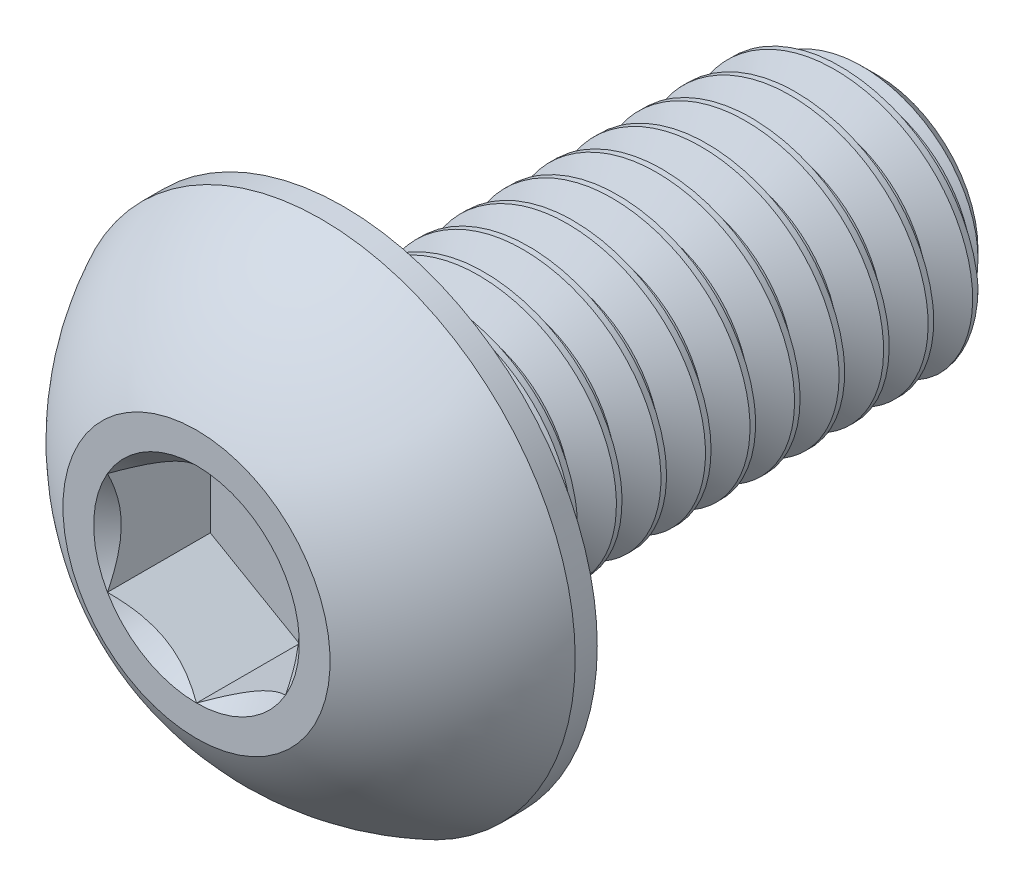
SolidWorks part; units mm, degrees
ref_plane "Front" through (0, 0, 0) normal (0, 0, 1) x (1, 0, 0)
ref_plane "Top" through (0, 0, 0) normal (0, 1, 0) x (1, 0, 0)
ref_plane "Right" through (0, 0, 0) normal (1, 0, 0) x (0, 0, -1)
sketch "Sketch1" plane through (0, 0, 0) normal (1, 0, 0) x (0, 0, -1)
  line L2 (1.65, 1.5) -> (7.65, 1.5)
  line L3 (7.65, 1.5) -> (7.65, 0)
  line L4 (7.65, 0) -> (1.65, 0)
  line L6 (1.4025, 2.85) -> (1.65, 2.85) construction
  line L7 (7.65, 1.5) -> (7.65, -1.5) construction
  line L8 (0, 0) -> (1.65, 0) construction
  line L9 (1.65, 2.85) -> (1.65, -2.85) construction
  line L11 (1.65, 1.5) -> (1.65, 0)
  line L13 (0, 1) -> (0, -1) construction
  line L14 (0, 1) -> (0, 1.5) construction
  line L15 (7.65, -1.5) -> (7.15, -1.5) construction
  arc A3 (0, 1.5) -> (1.4025, 2.85) centre (2.7948, 0) cw construction
  dimension "D1" = 0.2475
  dimension "Pitch" = 0.5
revolve "Revolve1" add sketch "Sketch1" angle 360 mid plane about L4
sketch "Sketch7" plane through (0, 0, 0) normal (1, 0, 0) x (0, 0, -1)
  line L6 (1.4025, 2.85) -> (1.65, 2.85) construction
  line L8 (0, 0) -> (1.65, 0) construction
  line L11 (1.65, 2.85) -> (1.65, -2.85) construction
  line L12 (1.4025, 2.85) -> (1.65, 2.85)
  line L13 (0, 0) -> (1.65, 0)
  line L14 (0, 1) -> (0, -1) construction
  line L15 (1.65, 2.85) -> (1.65, 0)
  line L16 (0, 1.5) -> (0, 0)
  arc A2 (1.4025, 2.85) -> (0, 1.5) centre (2.7948, 0) ccw construction
  arc A3 (1.4025, 2.85) -> (0, 1.5) centre (2.7948, 0) ccw
revolve "Revolve2" add sketch "Sketch7" angle 360 mid plane about L13
sketch "Sketch5" plane through (0, 0, 0) normal (0, 0, 1) x (1, 0, 0)
  line L1 (1, -0.5774) -> (1, 0.5774)
  line L2 (1, 0.5774) -> (0, 1.1547)
  line L3 (0, 1.1547) -> (-1, 0.5774)
  line L4 (-1, 0.5774) -> (-1, -0.5774)
  line L5 (-1, -0.5774) -> (0, -1.1547)
  line L6 (0, -1.1547) -> (1, -0.5774)
  circle A0 centre (0, 0) radius 1 construction
extrude "Cut-Extrude2" cut sketch "Sketch5" against normal blind 1.155
sketch "Sketch6" plane through (0, 0, 0) normal (0, 0, 1) x (1, 0, 0)
  circle A0 centre (0, 0) radius 1.1547
extrude "Cut-Extrude3" cut sketch "Sketch6" against normal blind 1.155 draft 45
sketch "Sketch11" plane through (0, 0, 0) normal (1, 0, 0) x (0, 0, -1)
  line L0 (1.65, -2.85) -> (1.65, 2.85)
  point P4 (1.65, 0)
split "Split1" trim tools "Sketch11" bodies to split 113 resulting bodies 119 120
sketch "Sketch10" plane through (0, 0, 0) normal (1, 0, 0) x (0, 0, -1)
  line L0 (7.65, 1.5) -> (7.65, -1.5) construction
  point P0 (6.9, -1.5)
  dimension "D1" = 0.75
sketch "Sketch3" plane through (0, 0, -7.65) normal (0, 0, -1) x (-1, 0, 0)
  circle A0 centre (0, 0) radius 1.5
curve "Helix/Spiral1" pitch 0.5 height 6.5 radius 1.5 centre (0, 0, -7.65) axis (0, 0, 1) start towards (0, 1, 0)
sketch "Sketch2" plane through (0, 0, 0) normal (1, 0, 0) x (0, 0, -1)
  line L0 (7.6187, 1.5541) -> (8.1187, 1.5541) construction
  line L1 (8.1187, 1.5541) -> (7.8687, 1.1211) construction
  line L2 (7.8687, 1.1211) -> (7.6187, 1.5541) construction
  line L3 (7.8687, 1.5541) -> (7.8687, 1.5) construction
  line L4 (7.8687, 1.5) -> (7.8687, 1.1752) construction
  line L5 (7.8687, 1.1752) -> (7.8687, 1.1211) construction
  line L6 (7.8375, 1.1752) -> (7.9, 1.1752)
  line L7 (7.65, 1.5) -> (8.0875, 1.5) construction
  line L8 (7.6344, 1.5271) -> (8.1031, 1.5271)
  line L9 (7.6344, 1.5271) -> (7.8375, 1.1752)
  line L10 (8.1031, 1.5271) -> (7.9, 1.1752)
  point P10 (7.8687, 1.1752)
  point P13 (7.8687, 1.5)
  point P16 (7.8687, 1.5271)
  dimension "D1" = 0.5
  dimension "D2" = 0.0625
chamfer "Chamfer1" distance 0.375 angle 45 1 edges at (0, 1.5, -7.65)
sweep "Cut-Sweep1" cut profiles "Sketch2" path "Helix/Spiral1" align with end faces yes
combine bodies "Combine1" operation type add bodies to combine 120 114
equation "\"D3@Helix/Spiral1\" = \"Lg@Sketch1\" + \"D4@Helix/Spiral1\""
equation "\"D1@Chamfer1\" = \"D4@Helix/Spiral1\" * .75"
equation "\"D1@Cut-Extrude2\" = \"Head Ht@Sketch1\" * .7"
equation "\"D1@Sketch1\" = \"Head Ht@Sketch1\" * .15"
equation "\"D1@Sketch10\" = \"D4@Helix/Spiral1\" * 1.5"
equation "\"D1@Cut-Extrude3\" = \"D1@Cut-Extrude2\""
equation "\"D4@Helix/Spiral1\"=\"Pitch@Sketch1\""
equation "\"D1@Sketch2\"=\"Pitch@Sketch1\""
equation "\"D2@Sketch2\"=\"D1@Sketch2\"/8"
